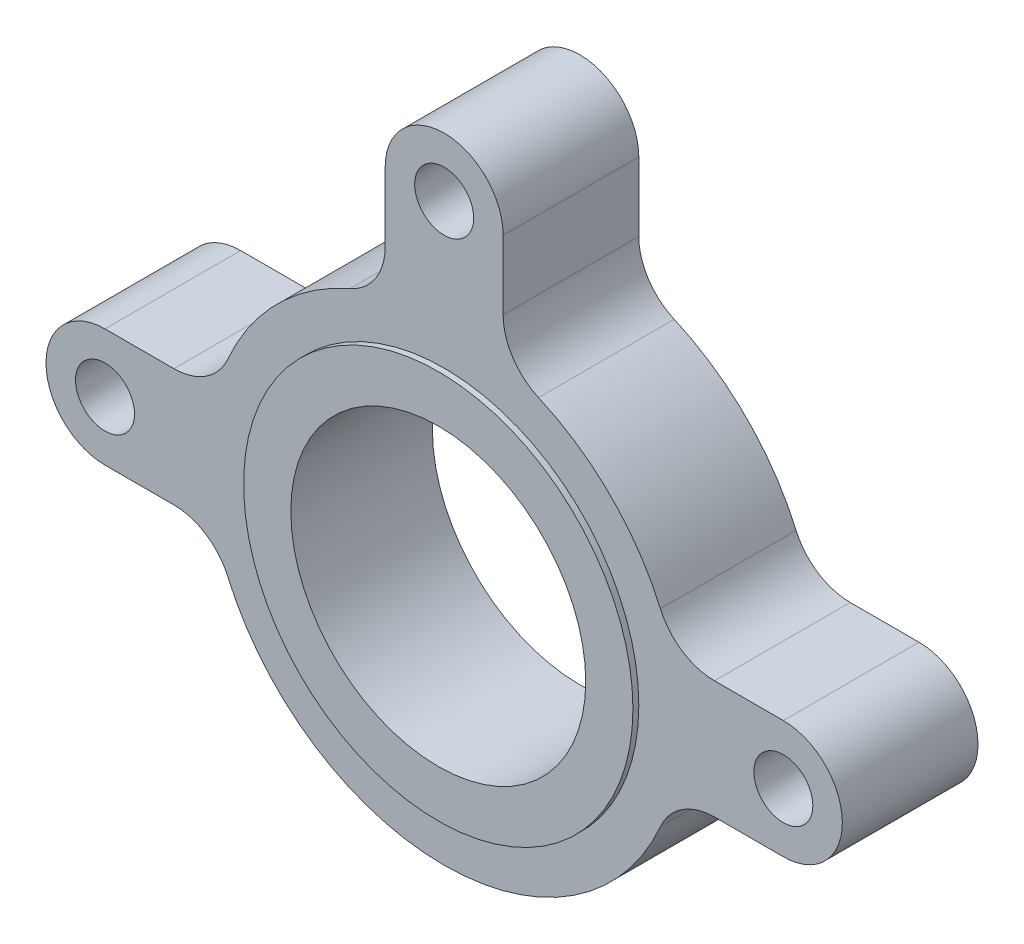
SolidWorks part; units mm, degrees
material "1.0045 (S355JR)"
ref_plane "Ön Düzlem" through (0, 0, 0) normal (0, 0, 1) x (1, 0, 0)
ref_plane "Üst Düzlem" through (0, 0, 0) normal (0, 1, 0) x (1, 0, 0)
ref_plane "Sağ Düzlem" through (0, 0, 0) normal (1, 0, 0) x (0, 0, -1)
sketch "Çizim1" plane through (0, 0, 0) normal (0, 0, 1) x (1, 0, 0)
  line L0 (-37.5, 37.5) -> (37.5, 37.5) construction
  line L1 (-37.5, 37.5) -> (-37.5, -37.5) construction
  line L2 (-37.5, -37.5) -> (37.5, -37.5) construction
  line L3 (37.5, 37.5) -> (37.5, -37.5) construction
  line L4 (-37.5, 37.5) -> (37.5, -37.5) construction
  line L5 (-37.5, -37.5) -> (37.5, 37.5) construction
  line L6 (37.5, -21.5) -> (-37.5, -21.5) construction
  line L7 (0, 37.5) -> (0, 20) construction
  line L8 (5, 28.75) -> (5, 22.9129)
  line L9 (-5, 28.75) -> (-5, 22.9129)
  line L10 (28.75, 5) -> (22.9129, 5)
  line L11 (28.75, -5) -> (22.9129, -5)
  line L12 (0, 28.75) -> (0, 0) construction
  line L14 (-28.75, -5) -> (-22.9129, -5)
  line L15 (-28.75, 5) -> (-22.9129, 5)
  line L16 (5, -28.75) -> (5, -19.3649) [skipped]
  line L17 (-5, -28.75) -> (-5, -19.3649) [skipped]
  circle A0 centre (0, 0) radius 12.5
  arc A1 (-8, 18.3303) -> (-18.3303, 8) centre (0, 0) ccw
  circle A2 centre (0, 28.75) radius 2.5
  arc A3 (5, 28.75) -> (-5, 28.75) centre (0, 28.75) ccw
  circle A4 centre (28.75, 0) radius 2.5
  arc A5 (28.75, -5) -> (28.75, 5) centre (28.75, 0) ccw
  circle A8 centre (-28.75, 0) radius 2.5
  arc A9 (-28.75, 5) -> (-28.75, -5) centre (-28.75, 0) ccw
  circle A10 centre (0, -28.75) radius 2.5 [skipped]
  circle A11 centre (0, -28.75) radius 5 [skipped]
  arc A12 (-18.3303, -8) -> (18.3303, -8) centre (0, 0) ccw
  arc A13 (18.3303, 8) -> (8, 18.3303) centre (0, 0) ccw
  arc A14 (22.9129, 5) -> (18.3303, 8) centre (22.9129, 10) cw
  arc A15 (22.9129, -5) -> (18.3303, -8) centre (22.9129, -10) ccw
  arc A16 (-22.9129, -5) -> (-18.3303, -8) centre (-22.9129, -10) cw
  arc A17 (-22.9129, 5) -> (-18.3303, 8) centre (-22.9129, 10) ccw
  arc A18 (-5, 22.9129) -> (-8, 18.3303) centre (-10, 22.9129) cw
  arc A19 (8, 18.3303) -> (5, 22.9129) centre (10, 22.9129) cw
  circle A20 centre (0, 0) radius 16.5
  point P0 (0, 0)
  point P40 (5, 19.3649)
  point P43 (0, 0)
  dimension "D1" = 25
  dimension "D3" = 40
  dimension "D4" = 5
  dimension "D5" = 33
  dimension "D2" = 16
  dimension "D6" = 4
extrude "Yükseklik-Ekstrüzyon2" add sketch "Çizim1" along normal blind 11.5 contours A13 A19 L8 A3 L9 A18 A1 A17 L15 A9 L14 A16 A12 A15 L11 A5 L10 A14 A20 A2 A4 A8 region at (4.1371, 25.8314, 0)
extrude "Yükseklik-Ekstrüzyon4" add sketch "Çizim1<4>" along normal blind 12 contours A20 A0 region at (-16.0333, 0, 0)
sketch "Çizim1<4>" plane through (0, 0, 0) normal (0, 0, 1) x (1, 0, 0) same geometry as "Çizim1"
